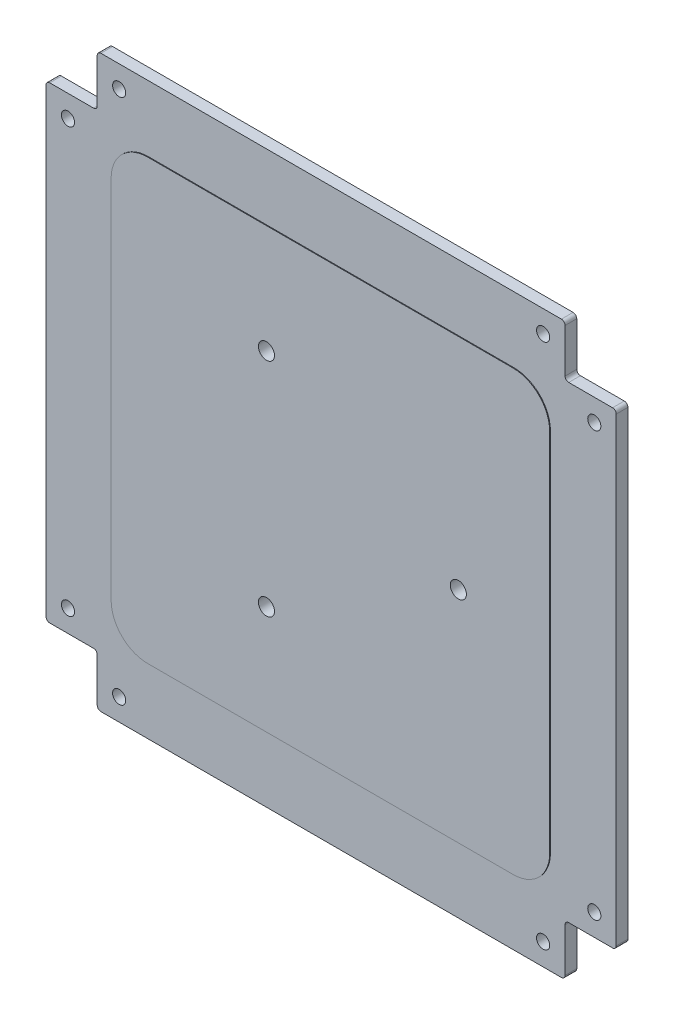
SolidWorks part; units mm, degrees
material "PET"
ref_plane "Front Plane" through (0, 0, 0) normal (0, 0, 1) x (1, 0, 0)
ref_plane "Top Plane" through (0, 0, 0) normal (0, 1, 0) x (1, 0, 0)
ref_plane "Right Plane" through (0, 0, 0) normal (1, 0, 0) x (0, 0, -1)
sketch "Sketch1" plane through (0, 0, 0) normal (0, 0, 1) x (1, 0, 0)
  line L0 (-32, 38.5) -> (-32, 32.5)
  line L1 (-31.5, -39) -> (31.5, -39)
  line L2 (-39, 31.5) -> (-39, -31.5)
  line L3 (-31.5, 39) -> (31.5, 39)
  line L4 (39, -31.5) -> (39, 31.5)
  line L5 (32, -38.5) -> (32, -32.5)
  line L6 (32.5, -32) -> (38.5, -32)
  line L7 (-32.5, 32) -> (-38.5, 32)
  line L8 (32, 38.5) -> (32, 32.5)
  line L9 (32.5, 32) -> (38.5, 32)
  line L10 (-38.5, -32) -> (-32.5, -32)
  line L11 (-32, -32.5) -> (-32, -38.5)
  line L12 (-32.5, -32.5) -> (32.5, 32.5) construction
  line L13 (32.5, -32.5) -> (-32.5, 32.5) construction
  arc A0 (-31.5, 39) -> (-32, 38.5) centre (-31.5, 38.5) ccw
  arc A1 (31.5, 39) -> (32, 38.5) centre (31.5, 38.5) cw
  arc A2 (32, 32.5) -> (32.5, 32) centre (32.5, 32.5) ccw
  arc A3 (38.5, 32) -> (39, 31.5) centre (38.5, 31.5) cw
  arc A4 (31.5, -39) -> (32, -38.5) centre (31.5, -38.5) ccw
  arc A5 (32.5, -32) -> (32, -32.5) centre (32.5, -32.5) ccw
  arc A6 (38.5, -32) -> (39, -31.5) centre (38.5, -31.5) ccw
  arc A7 (-32, -38.5) -> (-31.5, -39) centre (-31.5, -38.5) ccw
  arc A8 (-32, -32.5) -> (-32.5, -32) centre (-32.5, -32.5) ccw
  arc A9 (-39, -31.5) -> (-38.5, -32) centre (-38.5, -31.5) ccw
  arc A10 (-38.5, 32) -> (-39, 31.5) centre (-38.5, 31.5) ccw
  arc A11 (-32.5, 32) -> (-32, 32.5) centre (-32.5, 32.5) ccw
  point P0 (0, 0)
  dimension "D4" = 0.5
  dimension "D1" = 7
  dimension "D2" = 7
  dimension "D3" = 7
  dimension "D5" = 7
  dimension "D6" = 7
  dimension "D7" = 7
  dimension "D8" = 7
  dimension "D9" = 7
  dimension "D10" = 78
  dimension "D11" = 78
extrude "Boss-Extrude1" add sketch "Sketch1" along normal blind 1.6
sketch "Esboço1" plane through (0, 0, 1.6) normal (0, 0, 1) x (1, 0, 0)
  line L1 (-25, -30) -> (25, -30)
  line L2 (-30, -25) -> (-30, 25)
  line L3 (-25, 30) -> (25, 30)
  line L4 (30, -25) -> (30, 25)
  line L5 (-25, -25) -> (25, 25) construction
  line L6 (-25, 25) -> (25, -25) construction
  arc A0 (-30, 25) -> (-25, 30) centre (-25, 25) cw
  arc A1 (25, 30) -> (30, 25) centre (25, 25) cw
  arc A2 (30, -25) -> (25, -30) centre (25, -25) cw
  arc A3 (-25, -30) -> (-30, -25) centre (-25, -25) cw
  point P0 (0, 0)
  dimension "D1" = 5
  dimension "D2" = 60
  dimension "D3" = 60
extrude "Boss-Extrude2" add sketch "Esboço1" along normal blind 0.1
hole_wizard "M1.6 Hole1-FixingStructure" positions "Sketch3" profile "Sketch2" hole size "M1.6" standard "DIN"
sketch "Sketch3" plane through (0, 0, 0) normal (0, 0, -1) x (-1, 0, 0)
  line L0 (-31.5, 39) -> (31.5, 39) construction
  line L1 (31.5, -39) -> (-31.5, -39) construction
  line L2 (-39, -31.5) -> (-39, 31.5) construction
  line L3 (39, 31.5) -> (39, -31.5) construction
  line L4 (-31.5, 39) -> (31.5, 39) construction
  line L5 (31.5, -39) -> (-31.5, -39) construction
  line L6 (39, 31.5) -> (39, -31.5) construction
  line L7 (-39, -31.5) -> (-39, 31.5) construction
  point P0 (-29, 36)
  point P2 (29, 36)
  point P4 (-29, -36)
  point P6 (29, -36)
  point P20 (36, 29)
  point P22 (36, -29)
  point P24 (-36, -29)
  point P26 (-36, 29)
  dimension "D1" = 3
  dimension "D2" = 3
  dimension "D3" = 10
  dimension "D4" = 10
  dimension "D5" = 10
  dimension "D6" = 10
  dimension "D7" = 3
  dimension "D8" = 3
sketch "Sketch2" plane through (29, 36, 0) normal (1, 0, 0) x (0, 1, 0)
  line L0 (0, 0) -> (0, 200.5408)
  line L1 (0, 200.5408) -> (0.9, 200)
  line L2 (0.9, 200) -> (0.9, 0)
  line L5 (0.9, 0) -> (0, 0)
  line L10 (0, 200.5408) -> (-0.9, 200) construction
  line L11 (0, -6.35) -> (0, 107.95) construction
  dimension "Hole Dia." = 1.8
  dimension "Hole Depth" = 200
  dimension "Drill Angle" = 118
sketch "Sketch4" plane through (0, 0, 1.7) normal (0, 0, 1) x (1, 0, 0)
  circle A0 centre (-8.75, 15.1554) radius 1.1 construction
  circle A1 centre (-8.75, -15.1554) radius 1.1 construction
  circle A2 centre (17.5, 0) radius 1.1 construction
  circle A3 centre (-8.75, 15.1554) radius 1.1
  circle A4 centre (-8.75, -15.1554) radius 1.1
  circle A5 centre (17.5, 0) radius 1.1
extrude "Cut-Extrude1" cut sketch "Sketch4" against normal up to surface (1.7 mm away) up to face at (28.1, 36, 0)
